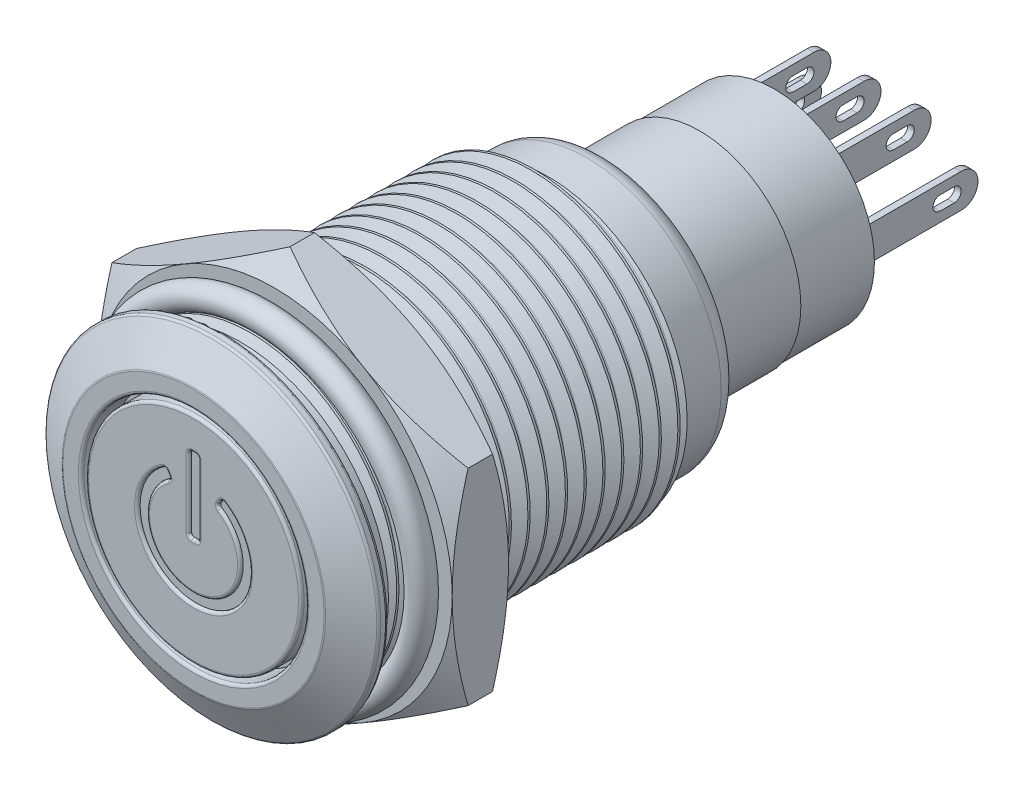
SolidWorks part; units mm, degrees
ref_plane "Спереди" through (0, 0, 0) normal (0, 0, 1) x (1, 0, 0)
ref_plane "Сверху" through (0, 0, 0) normal (0, 1, 0) x (1, 0, 0)
ref_plane "Справа" through (0, 0, 0) normal (1, 0, 0) x (0, 0, -1)
sketch "Эскиз1" plane through (0, 0, 0) normal (1, 0, 0) x (0, 0, -1)
  line L0 (-1.5, 0) -> (0, 0) construction
  line L1 (0, 0) -> (29.5, 0) construction
  line L2 (-1.5, 0) -> (-1.5, 7)
  line L3 (-1.5, 7) -> (-0.5, 8.9)
  line L4 (-0.5, 8.9) -> (0, 8.9)
  line L5 (0, 8.9) -> (0, 7.9)
  line L6 (0, 7.9) -> (17.067, 7.9)
  line L7 (17.067, 7.9) -> (17.5, 7.15)
  line L8 (17.5, 7.15) -> (19.5, 7.15)
  line L9 (20.5, 6.15) -> (20.5, 5.4)
  line L10 (20.5, 5.4) -> (25.5, 5.4)
  line L11 (25.5, 5.4) -> (25.5, 5.325)
  line L12 (25.5, 5.325) -> (29.5, 5.325)
  line L13 (29.5, 5.325) -> (29.5, 0)
  line L14 (-1.5, 0) -> (29.5, 0)
  line L15 (-1.5, 5.75) -> (0, 5.75)
  line L16 (-1.5, 5.75) -> (-1.5, 6)
  line L17 (-1.5, 6) -> (0, 6)
  line L18 (0, 5.75) -> (0, 6)
  line L20 (20.5, 5.4) -> (19.5, 5.4)
  line L21 (20.5, 5.4) -> (20.5, 5.9)
  line L22 (20.5, 5.9) -> (19.5, 5.9)
  line L23 (19.5, 5.4) -> (19.5, 5.9)
  arc A0 (19.5, 7.15) -> (20.5, 6.15) centre (19.5, 6.15) cw
  dimension "D16" = 1
  dimension "D1" = 10.65
  dimension "D2" = 10.8
  dimension "D3" = 14.3
  dimension "D4" = 15.8
  dimension "D5" = 1.5
  dimension "D6" = 14
  dimension "D7" = 0.5
  dimension "D8" = 17.8
  dimension "D9" = 11.5
  dimension "D10" = 0.25
  dimension "D11" = 4
  dimension "D12" = 9
  dimension "D13" = 31
  dimension "D14" = 19
  dimension "D15" = 120
  dimension "D17" = 1
  dimension "D18" = 0.5
revolve "Повернуть1" add sketch "Эскиз1" angle 360 about L1
fillet "Скругление1" radius 0.15 5 edges at (5.75, 0, 1.5) (6, 0, 1.5) (7, 0, 1.5) (8.9, 0, 0) (8.9, 0, 0.5)
sketch "Эскиз2" plane through (0, 0, 0) normal (0, 0, -1) x (-1, 0, 0)
  circle A0 centre (0, 0) radius 8
  dimension "D1" = 16
curve "Спираль1" pitch 1 height 20 turns 20
ref_plane "Плоскость1" through (-8, 0, 0) normal (0, -0.9998, -0.0199) x (-1, 0, 0)
sketch "Эскиз3" plane through (-8, 0, 0) normal (0, -0.9998, -0.0199) x (-1, 0, 0)
  line L0 (0, 0) -> (-0.7117, 0.4109)
  line L1 (-0.7117, 0.5841) -> (0, 0.995)
  line L2 (0, 0.995) -> (0, 0)
  arc A0 (-0.7117, 0.4109) -> (-0.7117, 0.5841) centre (-0.6617, 0.4975) cw
  point P2 (0, 0)
  point P4 (0, 0)
  dimension "D3" = 0.1
  dimension "D1" = 60
  dimension "D2" = 0.995
sweep "Вырез-По траектории1" cut profiles "Эскиз3" path "Спираль1"
sketch "Эскиз4" plane through (0, 0, 0) normal (1, 0, 0) x (0, 0, -1)
  line L0 (0, 0) -> (-3.0155, 0) construction
  line L1 (0.8077, 7.9) -> (0, 7.9) construction
  line L2 (0, 0) -> (1, 0)
  line L3 (0, 0) -> (0, 7.9)
  line L4 (0, 7.9) -> (1, 7.9)
  line L5 (1, 0) -> (1, 7.9)
  dimension "D1" = 1
revolve "Повернуть2" add sketch "Эскиз4" angle 360 about L0
sketch "Эскиз5" plane through (0, 0, 0) normal (0, 0, -1) x (-1, 0, 0)
  line L1 (9.5, -5.4848) -> (9.5, 5.4848)
  line L2 (9.5, 5.4848) -> (0, 10.9697)
  line L3 (0, 10.9697) -> (-9.5, 5.4848)
  line L4 (-9.5, 5.4848) -> (-9.5, -5.4848)
  line L5 (-9.5, -5.4848) -> (0, -10.9697)
  line L6 (0, -10.9697) -> (9.5, -5.4848)
  circle A0 centre (0, 0) radius 9.5 construction
  circle A1 centre (0, 0) radius 7.5
  dimension "D2" = 15
  dimension "D1" = 19
extrude "Бобышка-Вытянуть1" add sketch "Эскиз5" along normal blind 3 from offset 2.8 separate body
sketch "Эскиз6" plane through (0, 0, 0) normal (0, 1, 0) x (1, 0, 0)
  line L0 (0, 0) -> (0, 29.5) construction
  line L1 (5.325, 29.5) -> (-5.325, 29.5) construction
  line L2 (8.25, 2.8) -> (5.6519, 4.3)
  line L4 (5.6519, 4.3) -> (8.25, 5.8)
  line L5 (9.5, 5.8) -> (0, 5.8) construction
  line L6 (8.25, 5.8) -> (9.5, 5.8)
  line L7 (9.5, 5.8) -> (12.0981, 4.3)
  line L9 (12.0981, 4.3) -> (9.5, 2.8)
  line L10 (9.5, 2.8) -> (8.25, 2.8)
  line L11 (8.25, 5.8) -> (8.25, 2.8) construction
  line L12 (9.5, 2.8) -> (0, 2.8) construction
  line L13 (1.1041, 7.2091) -> (16.4501, 7.2091)
  line L14 (1.1041, 7.2091) -> (1.1041, 1.5348)
  line L15 (1.1041, 1.5348) -> (16.4501, 1.5348)
  line L16 (16.4501, 7.2091) -> (16.4501, 1.5348)
  spline S1 degree 2 poles (-7.2978, 1) (-6.7002, 1.0323) (-5.5993, 1.0621) (-3.2909, 1.1246) (-0.0186, 1.1871) (3.2536, 1.2496) (5.5729, 1.3121) (7.8923, 1.3746) (7.9, 1.4371) (7.9077, 1.4996) (5.5993, 1.5621) (3.2909, 1.6246) (0.0186, 1.6871) (-3.2536, 1.7496) (-5.5729, 1.8121) (-7.8923, 1.8746) (-7.9, 1.9371) (-7.9077, 1.9996) (-5.5993, 2.0621) (-3.2909, 2.1246) (-0.0186, 2.1871) (3.2536, 2.2496) (5.5729, 2.3121) (7.8923, 2.3746) (7.9, 2.4371) (7.9077, 2.4996) (5.5993, 2.5621) (3.2909, 2.6246) (0.0186, 2.6871) (-3.2536, 2.7496) (-5.5729, 2.8121) (-7.8923, 2.8746) (-7.9, 2.9371) (-7.9077, 2.9996) (-5.5993, 3.0621) (-3.2909, 3.1246) (-0.0186, 3.1871) (3.2536, 3.2496) (5.5729, 3.3121) (7.8923, 3.3746) (7.9, 3.4371) (7.9077, 3.4996) (5.5993, 3.5621) (3.2909, 3.6246) (0.0186, 3.6871) (-3.2536, 3.7496) (-5.5729, 3.8121) (-7.8923, 3.8746) (-7.9, 3.9371) (-7.9077, 3.9996) (-5.5993, 4.0621) (-3.2909, 4.1246) (-0.0186, 4.1871) (3.2536, 4.2496) (5.5729, 4.3121) (7.8923, 4.3746) (7.9, 4.4371) (7.9077, 4.4996) (5.5993, 4.5621) (3.2909, 4.6246) (0.0186, 4.6871) (-3.2536, 4.7496) (-5.5729, 4.8121) (-7.8923, 4.8746) (-7.9, 4.9371) (-7.9077, 4.9996) (-5.5993, 5.0621) (-3.2909, 5.1246) (-0.0186, 5.1871) (3.2536, 5.2496) (5.5729, 5.3121) (7.8923, 5.3746) (7.9, 5.4371) (7.9077, 5.4996) (5.5993, 5.5621) (3.2909, 5.6246) (0.0186, 5.6871) (-3.2536, 5.7496) (-5.5729, 5.8121) (-7.8923, 5.8746) (-7.9, 5.9371) (-7.9077, 5.9996) (-5.5993, 6.0621) (-3.2909, 6.1246) (-0.0186, 6.1871) (3.2536, 6.2496) (5.5729, 6.3121) (7.8923, 6.3746) (7.9, 6.4371) (7.9077, 6.4996) (5.5993, 6.5621) (3.2909, 6.6246) (0.0186, 6.6871) (-3.2536, 6.7496) (-5.5729, 6.8121) (-7.8923, 6.8746) (-7.9, 6.9371) (-7.9077, 6.9996) (-5.5993, 7.0621) (-3.2909, 7.1246) (-0.0186, 7.1871) (3.2536, 7.2496) (5.5729, 7.3121) (7.8923, 7.3746) (7.9, 7.4371) (7.9077, 7.4996) (5.5993, 7.5621) (3.2909, 7.6246) (0.0186, 7.6871) (-3.2536, 7.7496) (-5.5729, 7.8121) (-7.8923, 7.8746) (-7.9, 7.9371) (-7.9077, 7.9996) (-5.5993, 8.0621) (-3.2909, 8.1246) (-0.0186, 8.1871) (3.2536, 8.2496) (5.5729, 8.3121) (7.8923, 8.3746) (7.9, 8.4371) (7.9077, 8.4996) (5.5993, 8.5621) (3.2909, 8.6246) (0.0186, 8.6871) (-3.2536, 8.7496) (-5.5729, 8.8121) (-7.8923, 8.8746) (-7.9, 8.9371) (-7.9077, 8.9996) (-5.5993, 9.0621) (-3.2909, 9.1246) (-0.0186, 9.1871) (3.2536, 9.2496) (5.5729, 9.3121) (7.8923, 9.3746) (7.9, 9.4371) (7.9077, 9.4996) (5.5993, 9.5621) (3.2909, 9.6246) (0.0186, 9.6871) (-3.2536, 9.7496) (-5.5729, 9.8121) (-7.8923, 9.8746) (-7.9, 9.9371) (-7.9077, 9.9996) (-5.5993, 10.0621) (-3.2909, 10.1246) (-0.0186, 10.1871) (3.2536, 10.2496) (5.5729, 10.3121) (7.8923, 10.3746) (7.9, 10.4371) (7.9077, 10.4996) (5.5993, 10.5621) (3.2909, 10.6246) (0.0186, 10.6871) (-3.2536, 10.7496) (-5.5729, 10.8121) (-7.8923, 10.8746) (-7.9, 10.9371) (-7.9077, 10.9996) (-5.5993, 11.0621) (-3.2909, 11.1246) (-0.0186, 11.1871) (3.2536, 11.2496) (5.5729, 11.3121) (7.8923, 11.3746) (7.9, 11.4371) (7.9077, 11.4996) (5.5993, 11.5621) (3.2909, 11.6246) (0.0186, 11.6871) (-3.2536, 11.7496) (-5.5729, 11.8121) (-7.8923, 11.8746) (-7.9, 11.9371) (-7.9077, 11.9996) (-5.5993, 12.0621) (-3.2909, 12.1246) (-0.0186, 12.1871) (3.2536, 12.2496) (5.5729, 12.3121) (7.8923, 12.3746) (7.9, 12.4371) (7.9077, 12.4996) (5.5993, 12.5621) (3.2909, 12.6246) (0.0186, 12.6871) (-3.2536, 12.7496) (-5.5729, 12.8121) (-7.8923, 12.8746) (-7.9, 12.9371) (-7.9077, 12.9996) (-5.5993, 13.0621) (-3.2909, 13.1246) (-0.0186, 13.1871) (3.2536, 13.2496) (5.5729, 13.3121) (7.8923, 13.3746) (7.9, 13.4371) (7.9077, 13.4996) (5.5993, 13.5621) (3.2909, 13.6246) (0.0186, 13.6871) (-3.2536, 13.7496) (-5.5729, 13.8121) (-7.8923, 13.8746) (-7.9, 13.9371) (-7.9077, 13.9996) (-5.5993, 14.0621) (-3.2909, 14.1246) (-0.0186, 14.1871) (3.2536, 14.2496) (5.5729, 14.3121) (7.8923, 14.3746) (7.9, 14.4371) (7.9077, 14.4996) (5.5993, 14.5621) (3.2909, 14.6246) (0.0186, 14.6871) (-3.2536, 14.7496) (-5.5729, 14.8121) (-7.8923, 14.8746) (-7.9, 14.9371) (-7.9077, 14.9996) (-5.5993, 15.0621) (-3.2909, 15.1246) (-0.0186, 15.1871) (3.2536, 15.2496) (5.5729, 15.3121) (7.8923, 15.3746) (7.9, 15.4371) (7.9077, 15.4996) (5.5993, 15.5621) (3.2909, 15.6246) (0.0186, 15.6871) (-3.2536, 15.7496) (-5.5729, 15.8121) (-7.8923, 15.8746) (-7.9, 15.9371) (-7.9077, 15.9996) (-5.5993, 16.0621) (-3.2909, 16.1246) (-0.0186, 16.1871) (3.2536, 16.2496) (5.5729, 16.3121) (7.8923, 16.3746) (7.9, 16.4371) (7.9077, 16.4996) (5.5993, 16.5621) (3.2909, 16.6246) (0.0186, 16.6871) (-3.2536, 16.7496) (-5.5729, 16.8121) (-7.8923, 16.8746) (-7.9, 16.9371) (-7.9077, 16.9996) (-5.5993, 17.0621) (-5.509, 17.0645) (-5.4159, 17.067) knots 0.003146 0.003146 0.003146 0.00625 0.00625 0.0125 0.0125 0.01875 0.01875 0.025 0.025 0.03125 0.03125 0.0375 0.0375 0.04375 0.04375 0.05 0.05 0.05625 0.05625 0.0625 0.0625 0.06875 0.06875 0.075 0.075 0.08125 0.08125 0.0875 0.0875 0.09375 0.09375 0.1 0.1 0.10625 0.10625 0.1125 0.1125 0.11875 0.11875 0.125 0.125 0.13125 0.13125 0.1375 0.1375 0.14375 0.14375 0.15 0.15 0.15625 0.15625 0.1625 0.1625 0.16875 0.16875 0.175 0.175 0.18125 0.18125 0.1875 0.1875 0.19375 0.19375 0.2 0.2 0.20625 0.20625 0.2125 0.2125 0.21875 0.21875 0.225 0.225 0.23125 0.23125 0.2375 0.2375 0.24375 0.24375 0.25 0.25 0.25625 0.25625 0.2625 0.2625 0.26875 0.26875 0.275 0.275 0.28125 0.28125 0.2875 0.2875 0.29375 0.29375 0.3 0.3 0.30625 0.30625 0.3125 0.3125 0.31875 0.31875 0.325 0.325 0.33125 0.33125 0.3375 0.3375 0.34375 0.34375 0.35 0.35 0.35625 0.35625 0.3625 0.3625 0.36875 0.36875 0.375 0.375 0.38125 0.38125 0.3875 0.3875 0.39375 0.39375 0.4 0.4 0.40625 0.40625 0.4125 0.4125 0.41875 0.41875 0.425 0.425 0.43125 0.43125 0.4375 0.4375 0.44375 0.44375 0.45 0.45 0.45625 0.45625 0.4625 0.4625 0.46875 0.46875 0.475 0.475 0.48125 0.48125 0.4875 0.4875 0.49375 0.49375 0.5 0.5 0.50625 0.50625 0.5125 0.5125 0.51875 0.51875 0.525 0.525 0.53125 0.53125 0.5375 0.5375 0.54375 0.54375 0.55 0.55 0.55625 0.55625 0.5625 0.5625 0.56875 0.56875 0.575 0.575 0.58125 0.58125 0.5875 0.5875 0.59375 0.59375 0.6 0.6 0.60625 0.60625 0.6125 0.6125 0.61875 0.61875 0.625 0.625 0.63125 0.63125 0.6375 0.6375 0.64375 0.64375 0.65 0.65 0.65625 0.65625 0.6625 0.6625 0.66875 0.66875 0.675 0.675 0.68125 0.68125 0.6875 0.6875 0.69375 0.69375 0.7 0.7 0.70625 0.70625 0.7125 0.7125 0.71875 0.71875 0.725 0.725 0.73125 0.73125 0.7375 0.7375 0.74375 0.74375 0.75 0.75 0.75625 0.75625 0.7625 0.7625 0.76875 0.76875 0.775 0.775 0.78125 0.78125 0.7875 0.7875 0.79375 0.79375 0.8 0.8 0.80625 0.80625 0.806514 0.806514 0.806514 weights 0.961941 0.962193 1 0.92388 1 0.92388 1 0.92388 1 0.92388 1 0.92388 1 0.92388 1 0.92388 1 0.92388 1 0.92388 1 0.92388 1 0.92388 1 0.92388 1 0.92388 1 0.92388 1 0.92388 1 0.92388 1 0.92388 1 0.92388 1 0.92388 1 0.92388 1 0.92388 1 0.92388 1 0.92388 1 0.92388 1 0.92388 1 0.92388 1 0.92388 1 0.92388 1 0.92388 1 0.92388 1 0.92388 1 0.92388 1 0.92388 1 0.92388 1 0.92388 1 0.92388 1 0.92388 1 0.92388 1 0.92388 1 0.92388 1 0.92388 1 0.92388 1 0.92388 1 0.92388 1 0.92388 1 0.92388 1 0.92388 1 0.92388 1 0.92388 1 0.92388 1 0.92388 1 0.92388 1 0.92388 1 0.92388 1 0.92388 1 0.92388 1 0.92388 1 0.92388 1 0.92388 1 0.92388 1 0.92388 1 0.92388 1 0.92388 1 0.92388 1 0.92388 1 0.92388 1 0.92388 1 0.92388 1 0.92388 1 0.92388 1 0.92388 1 0.92388 1 0.92388 1 0.92388 1 0.92388 1 0.92388 1 0.92388 1 0.92388 1 0.92388 1 0.92388 1 0.92388 1 0.92388 1 0.92388 1 0.92388 1 0.92388 1 0.92388 1 0.92388 1 0.92388 1 0.92388 1 0.92388 1 0.92388 1 0.92388 1 0.92388 1 0.92388 1 0.92388 1 0.92388 1 0.92388 1 0.92388 1 0.92388 1 0.92388 1 0.92388 1 0.92388 1 0.92388 1 0.92388 1 0.92388 1 0.92388 1 0.92388 1 0.92388 1 0.92388 1 0.92388 1 0.92388 1 0.92388 1 0.92388 1 0.92388 1 0.92388 1 0.92388 1 0.92388 1 0.92388 1 0.92388 1 0.92388 1 0.92388 1 0.92388 1 0.92388 1 0.92388 1 0.92388 1 0.92388 1 0.92388 1 0.92388 1 0.996788 0.993847 construction
  dimension "D1" = 60
  dimension "D2" = 8.25
revolve "Вырез-Повернуть1" cut sketch "Эскиз6" angle 360 about L0
sketch "Эскиз7" plane through (0, 0, 0) normal (0, 1, 0) x (1, 0, 0)
  line L0 (0, 0) -> (0, 24.2687) construction
  line L1 (-8.25, 2.8) -> (8.25, 2.8) construction
  circle A0 centre (8.5, 2.15) radius 0.65
  point P5 (8.65, 2.0175)
  point P8 (8.5374, 2.15)
  dimension "D1" = 1.3
  dimension "D2" = 17
revolve "Повернуть3" add sketch "Эскиз7" angle 360 about L0
sketch "Эскиз8" plane through (0, 0, 1.5) normal (0, 0, 1) x (1, 0, 0)
  line L0 (-8.6355, 14.9571) -> (0, 0)
  line L1 (0, 0) -> (8.6355, 14.9571)
  line L2 (8.6355, 14.9571) -> (-8.6355, 14.9571)
  line L3 (0, 0) -> (0, 4)
  line L4 (0.25, 0) -> (0.25, 4)
  line L5 (-0.25, 0) -> (-0.25, 4)
  line L6 (0.25, 0) -> (-0.25, 0)
  line L7 (0.25, 4) -> (-0.25, 4)
  line L8 (-1.5, 2.5981) -> (-1.25, 2.1651)
  line L9 (1.5, 2.5981) -> (1.25, 2.1651)
  arc A0 (-1.375, 2.3816) -> (1.375, 2.3816) centre (0, 0) ccw
  arc A1 (-1.5, 2.5981) -> (1.5, 2.5981) centre (0, 0) ccw
  arc A2 (-1.25, 2.1651) -> (1.25, 2.1651) centre (0, 0) ccw
  point P4 (0, 4.686)
  dimension "D2" = 5.5
  dimension "D1" = 60
  dimension "D3" = 4
  dimension "D4" = 0.25
  dimension "D5" = 0.25
  dimension "D6" = 0.25
  dimension "D7" = 0.25
extrude "Вырез-Вытянуть1" cut sketch "Эскиз8" against normal blind 0.15 contours L4 L7 L3 L1 | L3 L7 L5 L0 | L6 L4 L1 | L6 L0 L5 | A2 L8 A0 L1 | L0 A1 L9 A0
fillet "Скругление2" radius 0.15 8 edges at (0, 4, 1.5) (-1.375, 2.3816, 1.5) (0.25, 2, 1.5) (-0.25, 2, 1.5) (0, -2.5, 1.5) (0, -3, 1.5) (0, 0, 1.5) (1.375, 2.3816, 1.5)
sketch "Эскиз9" plane through (0, 0, -29.5) normal (0, 0, -1) x (-1, 0, 0)
  line L0 (-4, 0) -> (0, 0) construction
  line L1 (-4.35, 0.9) -> (-4, 0.9)
  line L2 (-4.35, 0.9) -> (-4.35, -0.9)
  line L3 (-4.35, -0.9) -> (-4, -0.9)
  line L4 (-4, 0.9) -> (-4, -0.9)
  line L5 (-2.85, 3.475) -> (-2.5, 3.475)
  line L6 (-2.85, 3.475) -> (-2.85, 1.675)
  line L7 (-2.85, 1.675) -> (-2.5, 1.675)
  line L8 (-2.5, 3.475) -> (-2.5, 1.675)
  line L9 (-0.175, 3.475) -> (0.175, 3.475)
  line L10 (-0.175, 3.475) -> (-0.175, 1.675)
  line L11 (-0.175, 1.675) -> (0.175, 1.675)
  line L12 (0.175, 3.475) -> (0.175, 1.675)
  line L13 (2.5, 3.475) -> (2.85, 3.475)
  line L14 (2.5, 3.475) -> (2.5, 1.675)
  line L15 (2.5, 1.675) -> (2.85, 1.675)
  line L16 (2.85, 3.475) -> (2.85, 1.675)
  line L17 (4, 0.9) -> (4.35, 0.9)
  line L18 (4, 0.9) -> (4, -0.9)
  line L19 (4, -0.9) -> (4.35, -0.9)
  line L20 (4.35, 0.9) -> (4.35, -0.9)
  line L21 (0, 0) -> (4, 0) construction
  line L22 (0, 0) -> (0, 1.675) construction
  line L23 (-2.5, 1.675) -> (-0.175, 1.675) construction
  line L24 (0.175, 1.675) -> (2.5, 1.675) construction
  line L25 (0, 0) -> (0, -5.325) construction
  circle A0 centre (0, 0) radius 5.325 construction
  dimension "D1" = 0.35
  dimension "D2" = 1.8
  dimension "D3" = 1.8
  dimension "D4" = 8.7
  dimension "D5" = 5.7
  dimension "D6" = 8.8
extrude "Бобышка-Вытянуть2" add sketch "Эскиз9" along normal blind 6.5 separate body
sketch "Эскиз10" plane through (-4.35, 0, 0) normal (-1, 0, 0) x (0, 0, 1)
  line L0 (-36, 1.675) -> (-29.5, 1.675) construction
  line L1 (-36, 3.475) -> (-35, 3.475)
  line L2 (-36, 3.475) -> (-36, 1.675)
  line L3 (-36, 1.675) -> (-35, 1.675)
  line L4 (-35, 3.475) -> (-35, 1.675)
  dimension "D1" = 1
extrude "Вырез-Вытянуть2" cut sketch "Эскиз10" against normal through all
sketch "Эскиз11" plane through (-4.35, 0, 0) normal (-1, 0, 0) x (0, 0, 1)
  line L0 (-36, 0) -> (-35.1, 0) construction
  line L1 (-36, -0.9) -> (-36, 0.9) construction
  line L2 (-36, 0.9) -> (-29.5, 0.9) construction
  line L3 (-35, 3.475) -> (-35, 1.675) construction
  line L4 (-35, 2.575) -> (-34.1, 2.575) construction
  line L5 (-35, 3.475) -> (-29.5, 3.475) construction
  line L6 (-34.1, 3.475) -> (-37, 3.475)
  line L7 (-37, 3.475) -> (-37, -0.9)
  line L8 (-37, -0.9) -> (-35.1, -0.9)
  line L9 (-35.1, 0.9) -> (-34.1, 1.675)
  line L10 (-34.1, 2.575) -> (-33.35, 2.575) construction
  line L11 (-32.975, 2.575) -> (-33.725, 2.575) construction
  line L12 (-35.1, 0) -> (-34.35, 0) construction
  line L13 (-32.975, 2.2) -> (-33.725, 2.2)
  line L14 (-32.975, 2.95) -> (-33.725, 2.95)
  line L15 (-33.975, 0) -> (-34.725, 0) construction
  line L16 (-33.975, -0.375) -> (-34.725, -0.375)
  line L17 (-33.975, 0.375) -> (-34.725, 0.375)
  arc A0 (-34.1, 3.475) -> (-34.1, 1.675) centre (-34.1, 2.575) ccw
  arc A1 (-35.1, 0.9) -> (-35.1, -0.9) centre (-35.1, 0) ccw
  arc A2 (-32.975, 2.2) -> (-32.975, 2.95) centre (-32.975, 2.575) ccw
  arc A3 (-33.725, 2.95) -> (-33.725, 2.2) centre (-33.725, 2.575) ccw
  arc A4 (-33.975, -0.375) -> (-33.975, 0.375) centre (-33.975, 0) ccw
  arc A5 (-34.725, 0.375) -> (-34.725, -0.375) centre (-34.725, 0) ccw
  point P23 (-33.35, 2.575)
  point P29 (-34.35, 0)
  point P35 (0, 0)
  point P36 (0, 0)
  dimension "D1" = 1
  dimension "D2" = 0.75
  dimension "D3" = 0.75
extrude "Вырез-Вытянуть3" cut sketch "Эскиз11" against normal through all
